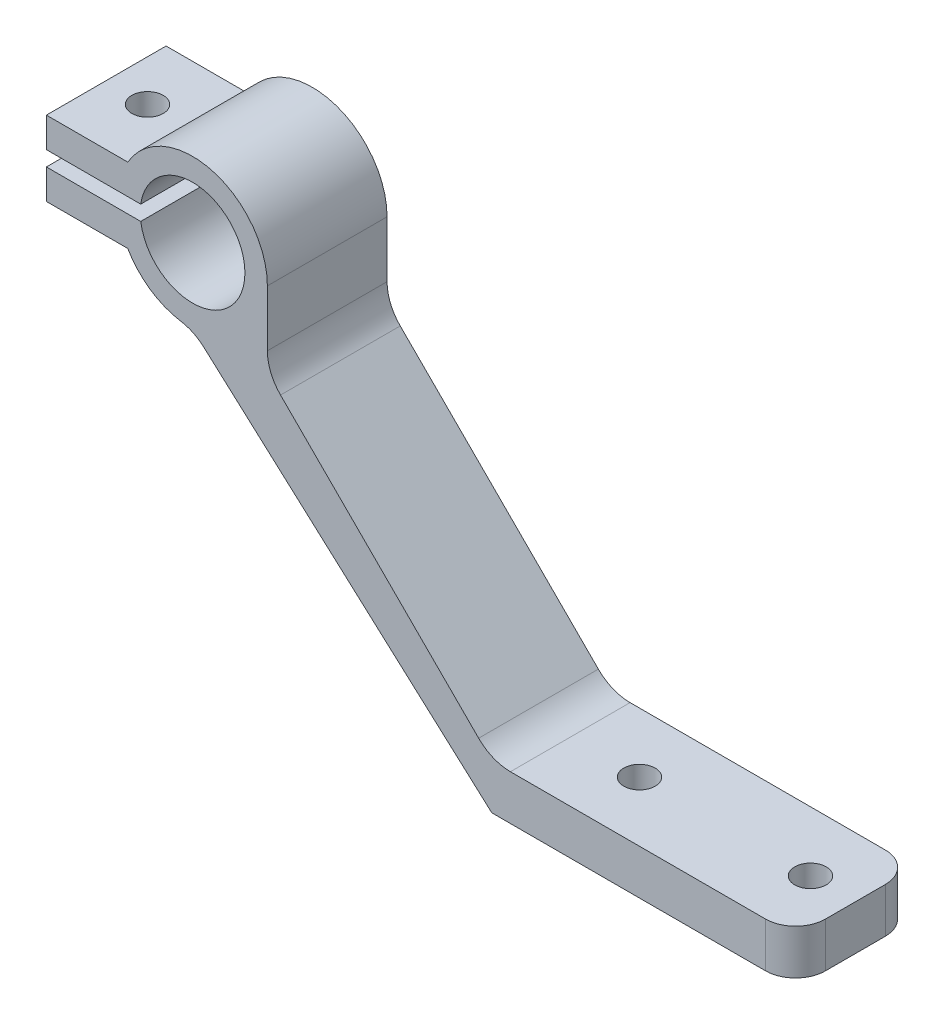
SolidWorks part; units mm, degrees
ref_plane "Front Plane" through (0, 0, 0) normal (0, 0, 1) x (1, 0, 0)
ref_plane "Top Plane" through (0, 0, 0) normal (0, 1, 0) x (1, 0, 0)
ref_plane "Right Plane" through (0, 0, 0) normal (1, 0, 0) x (0, 0, -1)
sketch "Sketch1" plane through (0, 0, 0) normal (0, 1, 0) x (1, 0, 0)
  line L0 (-5.715, 0) -> (5.715, 0)
  line L1 (-6.715, -4) -> (6.715, -4)
  line L2 (-8.715, -2) -> (-8.715, 2) construction
  line L3 (-6.715, 4) -> (6.715, 4)
  line L4 (8.715, -2) -> (8.715, 2)
  line L5 (-8.715, -4) -> (8.715, 4) construction
  line L6 (-8.715, 4) -> (8.715, -4) construction
  line L7 (-6.715, 4) -> (-11.585, 4)
  line L8 (-11.585, 4) -> (-11.585, -4)
  line L9 (-11.585, -4) -> (-6.715, -4)
  circle A0 centre (-5.715, 0) radius 1.05
  circle A1 centre (5.715, 0) radius 1.05
  arc A2 (6.715, 4) -> (8.715, 2) centre (6.715, 2) cw
  arc A3 (6.715, -4) -> (8.715, -2) centre (6.715, -2) ccw
  arc A4 (-6.715, -4) -> (-7.8876, -3.6202) centre (-6.715, -2) cw construction
  arc A5 (-7.8876, 3.6202) -> (-6.715, 4) centre (-6.715, 2) cw construction
  arc A6 (-8.715, 2) -> (-7.8876, 3.6202) centre (-6.715, 2) cw construction
  arc A7 (-7.8876, -3.6202) -> (-8.715, -2) centre (-6.715, -2) cw construction
  point P0 (0, 0)
  point P22 (-11.585, -4)
  point P23 (-11.5076, -4)
  point P24 (-14.9322, -4)
  point P28 (-11.585, 4)
  point P31 (-11.4574, 4)
  dimension "D4" = 2.1
  dimension "D5" = 2
  dimension "D1" = 3
  dimension "D2" = 4
  dimension "D3" = 11.43
  dimension "D6" = 5.87
extrude "Boss-Extrude1" add sketch "Sketch1" along normal blind 3 contours A5 L2 A4 L1 A3 L4 A2 L3 A1 A0 region at (-9.15, 0, 3.7818)
sketch "Sketch3" plane through (0, 0, 0) normal (0, 0, 1) x (1, 0, 0)
  line L2 (-41.3547, 21.5) -> (-36.3547, 21.5) construction
  line L3 (-41.3547, 21.5) -> (-41.3547, 22.5)
  line L4 (-36.3547, 21.5) -> (-36.3547, 22.5) construction
  line L5 (-41.3547, 24.5) -> (-36.3547, 24.5) construction
  line L6 (-41.3547, 21.5) -> (-36.3547, 24.5) construction
  line L7 (-36.3547, 21.5) -> (-41.3547, 24.5) construction
  line L8 (-41.3547, 25.5) -> (-36.3547, 25.5)
  line L9 (-41.3547, 22.5) -> (-36.3547, 22.5)
  line L10 (-41.3547, 23.5) -> (-36.3547, 23.5)
  line L11 (-41.3547, 20.5) -> (-36.3547, 20.5)
  line L12 (-36.3547, 20.5) -> (-35.9151, 20.5)
  line L13 (-41.3547, 20.5) -> (-41.3547, 21.5)
  line L14 (-41.3547, 24.5) -> (-41.3547, 25.5)
  line L15 (-36.3547, 25.5) -> (-35.9151, 25.5)
  line L16 (-36.3547, 23.5) -> (-35.0491, 23.5)
  line L17 (-36.3547, 22.5) -> (-35.0491, 22.5)
  line L18 (-41.3547, 22.5) -> (-41.3547, 23.5) construction
  line L19 (-41.3547, 23.5) -> (-41.3547, 24.5)
  line L20 (-36.3547, 22.5) -> (-36.3547, 23.5) construction
  line L21 (-36.3547, 23.5) -> (-36.3547, 24.5) construction
  line L22 (-26.585, 23) -> (-26.585, 18)
  line L23 (-26.585, 18) -> (-31.585, 18)
  arc A0 (-35.9151, 20.5) -> (-31.585, 18) centre (-31.585, 23) ccw
  circle A1 centre (-31.585, 23) radius 3.5
  arc A2 (-36.5599, 23.5) -> (-36.5599, 22.5) centre (-31.585, 23) ccw construction
  arc A3 (-36.5599, 22.5) -> (-36.3547, 21.5) centre (-31.585, 23) ccw construction
  arc A4 (-36.3547, 21.5) -> (-35.9151, 20.5) centre (-31.585, 23) ccw construction
  arc A5 (-36.3547, 24.5) -> (-36.5599, 23.5) centre (-31.585, 23) ccw construction
  arc A6 (-35.9151, 25.5) -> (-36.3547, 24.5) centre (-31.585, 23) ccw construction
  arc A7 (-31.585, 18) -> (-26.585, 23) centre (-31.585, 23) ccw construction
  arc A8 (-26.585, 23) -> (-35.9151, 25.5) centre (-31.585, 23) ccw
  point P6 (-38.8547, 23)
  point P26 (-23.215, 17.5)
  point P27 (-23.3843, 21.646)
  point P30 (-11.585, 3)
  point P32 (-11.585, 0)
  point P33 (-11.585, 0)
  dimension "D1" = 7
  dimension "D2" = 1.5
  dimension "D3" = 20
  dimension "D4" = 20
  dimension "D5" = 3
  dimension "D6" = 5
  dimension "D7" = 1
  dimension "D8" = 1
extrude "Boss-Extrude2" add sketch "Sketch3" along normal blind 4 and the other way blind 4 separate body contours A0 A1 region at (-41.1763, 22, 0)
loft "Loft2" add section face at (-29.085, 18, 0) section face at (-11.585, 1.5, 0) connector at (-26.585, 18, -4) connector at (-11.585, 3, -4)
fillet "Fillet1" radius 3 3 edges at (-11.585, 3, 0)
sketch "Sketch5" plane through (-4.2925, -4.2925, 0) normal (0.7071, 0.7071, 0) x (0, 0, -1)
  line L0 (0, 30.2837) -> (0, 11.5558)
  line L1 (4, 30.2837) -> (-4, 30.2837) construction
  line L2 (-4, 11.5558) -> (4, 11.5558) construction
  point P7 (0, 0)
  point P8 (0, 0)
ref_plane "Plane1" through (0, 0, 0) normal (0, 0, 1) x (0.7071, -0.7071, 0)
sketch "Sketch7" plane through (0, 0, 0) normal (0, 0, 1) x (0.7071, -0.7071, 0)
  line L0 (-35.0619, -2.535) -> (-8.3191, -4.0765)
  line L1 (-9.4345, -5.1918) -> (2.6269, 6.8695) construction
  line L2 (-5.42, -1.1773) -> (-6.9049, -2.6623) construction
  line L3 (-5.42, -1.1773) -> (-6.9049, -2.6623) construction
  arc A0 (-35.0619, -2.535) -> (-43.4271, -7.3646) centre (-38.5974, -6.0705) ccw construction
  point P7 (-38.0519, -1.1004)
  point P10 (-35.0844, -2.5126)
  point P11 (0, 0)
  dimension "D1" = 2
rib "Rib5" [suppressed] sketch "Sketch7" sketch "Sketch7" thickness 2 extrusion direction parallel to sketch draft on yes draft angle 10 parameters "D1"=2, "D3"=10
sketch "Sketch8" plane through (0, 25.5, 0) normal (0, 1, 0) x (1, 0, 0)
  circle A0 centre (-38.5942, 0) radius 1.05
  dimension "D1" = 2.1
extrude "Cut-Extrude1" cut sketch "Sketch8" against normal through all both and the other way through all
sketch "Sketch9" plane through (0, 20.5, 0) normal (0, -1, 0) x (1, 0, 0)
  line L1 (-36.5942, 1.1547) -> (-38.5942, 2.3094)
  line L2 (-38.5942, 2.3094) -> (-40.5942, 1.1547)
  line L3 (-40.5942, 1.1547) -> (-40.5942, -1.1547)
  line L4 (-40.5942, -1.1547) -> (-38.5942, -2.3094)
  line L5 (-38.5942, -2.3094) -> (-36.5942, -1.1547)
  line L6 (-36.5942, -1.1547) -> (-36.5942, 1.1547)
  circle A0 centre (-38.5942, 0) radius 2 construction
  dimension "D1" = 4
extrude "Cut-Extrude2" cut sketch "Sketch9" against normal blind 0.8
